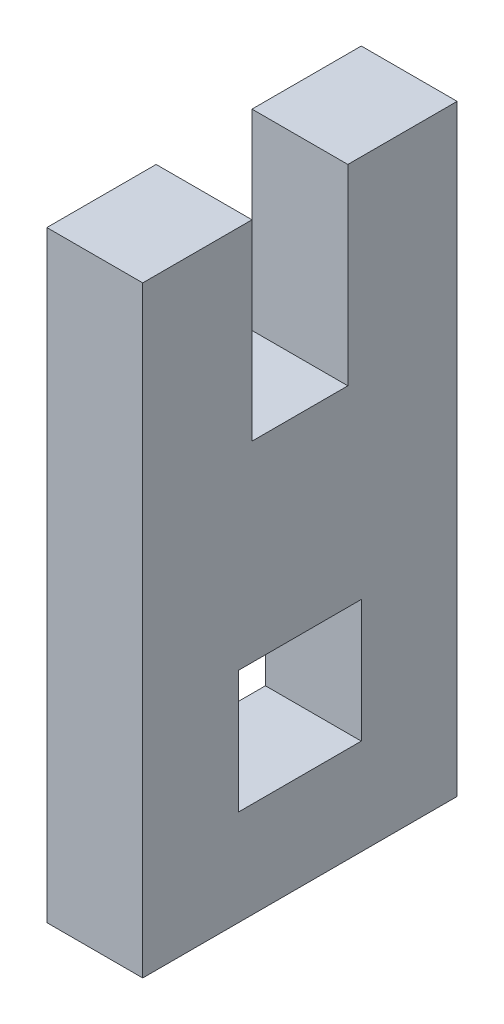
SolidWorks part; units mm, degrees
material "Balsa"
ref_plane "Front Plane" through (0, 0, 0) normal (0, 0, 1) x (1, 0, 0)
ref_plane "Top Plane" through (0, 0, 0) normal (0, 1, 0) x (1, 0, 0)
ref_plane "Right Plane" through (0, 0, 0) normal (1, 0, 0) x (0, 0, -1)
sketch "Sketch2" plane through (0, 0, 0) normal (1, 0, 0) x (0, 0, -1)
  line L0 (0, 0) -> (0, 39.878)
  line L1 (0, 39.878) -> (7.239, 39.878)
  line L2 (7.239, 39.878) -> (7.239, 27.178)
  line L3 (7.239, 27.178) -> (13.589, 27.178)
  line L4 (13.589, 27.178) -> (13.589, 39.878)
  line L5 (13.589, 39.878) -> (20.828, 39.878)
  line L6 (20.828, 39.878) -> (20.828, 0)
  line L7 (20.828, 0) -> (0, 0)
  line L9 (6.35, 6.35) -> (14.478, 6.35)
  line L10 (6.35, 6.35) -> (6.35, 14.478)
  line L11 (6.35, 14.478) -> (14.478, 14.478)
  line L12 (14.478, 6.35) -> (14.478, 14.478)
  point P13 (10.414, 27.178)
  point P16 (10.414, 0)
  dimension "D1" = 6.35
  dimension "D2" = 8.128
  dimension "D3" = 8.128
  dimension "D4" = 6.35
  dimension "D5" = 6.35
  dimension "D6" = 6.35
  dimension "D7" = 12.7
  dimension "D8" = 12.7
extrude "Boss-Extrude1" add sketch "Sketch2" along normal blind 6.35
equation "\"D4@Sketch2\"=\"D5@Sketch2\""
equation "\"D6@Sketch2\"=\"D5@Sketch2\""
